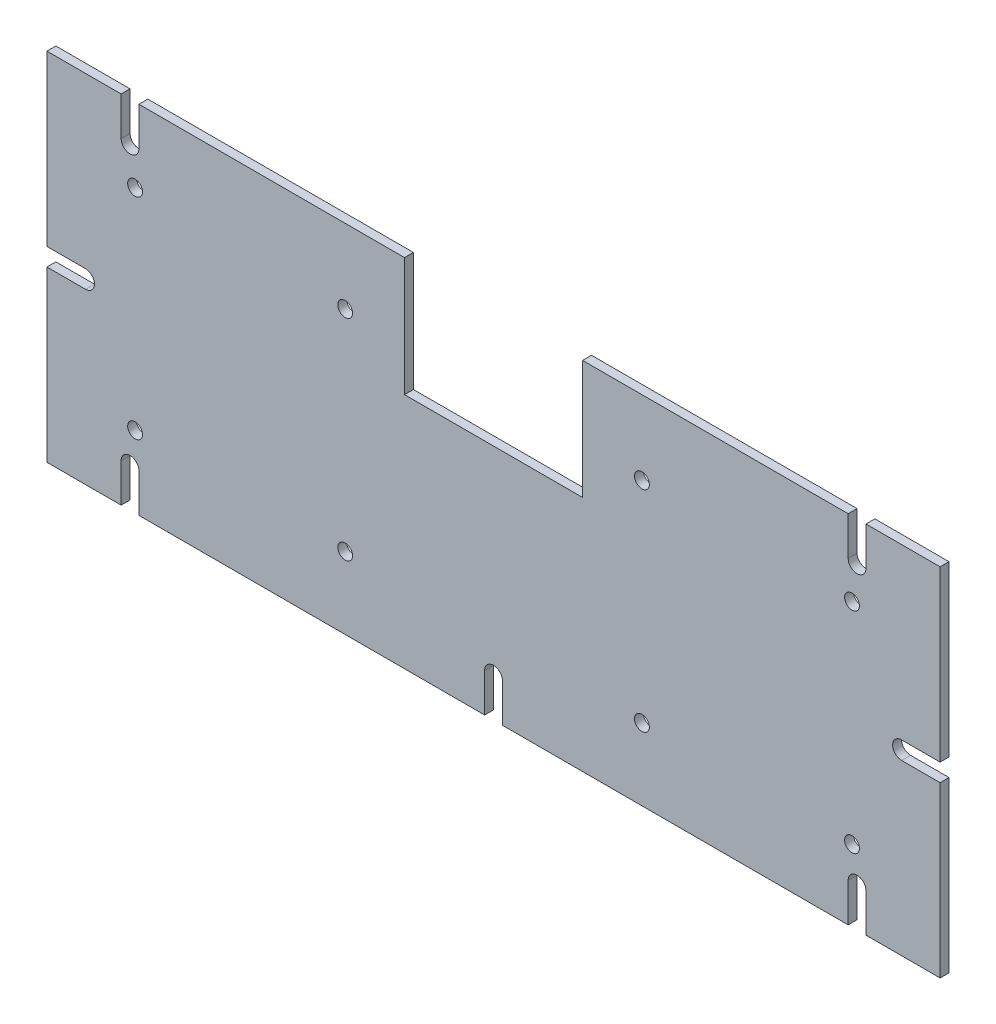
SolidWorks part; units mm, degrees
ref_plane "Front Plane" through (0, 0, 0) normal (0, 0, 1) x (1, 0, 0)
ref_plane "Top Plane" through (0, 0, 0) normal (0, 1, 0) x (1, 0, 0)
ref_plane "Right Plane" through (0, 0, 0) normal (1, 0, 0) x (0, 0, -1)
sketch "Sketch1" plane through (0, 0, 0) normal (0, 0, 1) x (1, 0, 0)
  line L1 (-150.5, -60) -> (150.5, -60)
  line L2 (-150.5, -60) -> (-150.5, 60)
  line L3 (-150.5, 60) -> (150.5, 60)
  line L4 (150.5, -60) -> (150.5, 60)
  line L5 (-150.5, -60) -> (150.5, 60) construction
  line L6 (-150.5, 60) -> (150.5, -60) construction
  point P0 (0, 0)
  dimension "D1" = 301
  dimension "D2" = 120
extrude "Boss-Extrude1" add sketch "Sketch1" along normal blind 3
sketch "Sketch2" plane through (0, 0, 3) normal (0, 0, 1) x (1, 0, 0)
  line L0 (-30, 60) -> (-30, 20)
  line L1 (150.5, 60) -> (-150.5, 60) construction
  line L2 (-30, 20) -> (30, 20)
  line L3 (0, 0) -> (0, 23.4463) construction
  line L4 (30, 60) -> (30, 20)
  line L5 (-30, 60) -> (30, 60)
  line L6 (-150.5, -60) -> (150.5, -60) construction
  point P9 (0, 20)
  point P12 (0, -60)
  dimension "D1" = 30
  dimension "D2" = 40
extrude "Cut-Extrude1" cut sketch "Sketch2" against normal blind 3 contours L5 L4 L2 L0
sketch "Sketch4" plane through (0, 0, 3) normal (0, 0, 1) x (1, 0, 0)
  line L0 (0, 0) -> (0, 20) construction
  line L1 (-30, 20) -> (30, 20) construction
  line L2 (0, 20) -> (0, -60) construction
  line L3 (-150.5, -60) -> (150.5, -60) construction
  line L4 (0, -60) -> (0, 60) construction
  line L5 (-150.5, 0) -> (150.5, 0) construction
  line L6 (150.5, -60) -> (150.5, 60) construction
  line L7 (-125.5, -60) -> (-125.5, -47)
  line L8 (-119.5, -47) -> (-119.5, -60)
  line L9 (-119.5, -60) -> (-125.5, -60)
  line L10 (-150.5, 60) -> (-150.5, -60) construction
  line L11 (3, -47) -> (3, -60)
  line L12 (-3, -60) -> (-3, -47)
  line L13 (3, -60) -> (-3, -60)
  line L14 (125.5, -47) -> (125.5, -60)
  line L15 (119.5, -60) -> (119.5, -47)
  line L16 (125.5, -60) -> (119.5, -60)
  line L17 (0, -20) -> (0, 60) construction
  line L18 (125.5, 60) -> (119.5, 60)
  line L19 (119.5, 60) -> (119.5, 47)
  line L20 (125.5, 47) -> (125.5, 60)
  line L21 (3, 60) -> (-3, 60)
  line L22 (-3, 60) -> (-3, 47)
  line L23 (3, 47) -> (3, 60)
  line L24 (-119.5, 60) -> (-125.5, 60)
  line L25 (-119.5, 47) -> (-119.5, 60)
  line L26 (-125.5, 60) -> (-125.5, 47)
  line L27 (150.5, 3) -> (137.5, 3)
  line L28 (137.5, -3) -> (150.5, -3)
  line L29 (150.5, -3) -> (150.5, 3)
  line L30 (150.5, 3) -> (150.5, -3)
  line L31 (137.5, 3) -> (150.5, 3)
  line L32 (150.5, -3) -> (137.5, -3)
  line L33 (-150.5, -3) -> (-137.5, -3)
  line L34 (-137.5, 3) -> (-150.5, 3)
  line L35 (-150.5, 3) -> (-150.5, -3)
  line L36 (-150.5, -3) -> (-150.5, 3)
  line L37 (-137.5, -3) -> (-150.5, -3)
  line L38 (-150.5, 3) -> (-137.5, 3)
  arc A0 (-125.5, -47) -> (-119.5, -47) centre (-122.5, -47) cw
  arc A1 (-3, -47) -> (3, -47) centre (0, -47) cw
  arc A2 (119.5, -47) -> (125.5, -47) centre (122.5, -47) cw
  arc A3 (119.5, 47) -> (125.5, 47) centre (122.5, 47) ccw
  arc A4 (-3, 47) -> (3, 47) centre (0, 47) ccw
  arc A5 (-125.5, 47) -> (-119.5, 47) centre (-122.5, 47) ccw
  arc A6 (137.5, 3) -> (137.5, -3) centre (137.5, 0) ccw
  arc A7 (-137.5, 3) -> (-137.5, -3) centre (-137.5, 0) cw
  line M21 (-150.5, 60) -> (-150.5, -60)
  line M22 (-150.5, -60) -> (150.5, -60)
  line M23 (150.5, -60) -> (150.5, 60)
  line M24 (150.5, 60) -> (30, 60)
  dimension "D1" = 3
  dimension "D2" = 13
  dimension "D3" = 25
  dimension "D5" = 6
  dimension "D6" = 13
  dimension "D4" = 3
extrude "Cut-Extrude2" cut sketch "Sketch4" against normal blind 10 contours A0 L7 L8 M22 | A7 L34 L33 M21 | A2 L15 L14 M22 | L27 A6 L28 M23 | L19 A3 L20 M24 | L25 L24 L26 A5 | L11 L13 L12 A1 region at (122.5, 52.3073, 3) region at (142.8073, 0, 3) region at (122.5, -52.3073, 3) region at (-122.5, -52.3073, 3) region at (-142.8073, 0, 3)
sketch "Sketch5" plane through (0, 0, 3) normal (0, 0, 1) x (1, 0, 0)
  line L0 (30, 60) -> (30, 20) construction
  line L1 (120.8, -35.8) -> (50, -35.8) construction
  line L2 (120.8, -35.8) -> (120.8, 35) construction
  line L3 (120.8, 35) -> (50, 35) construction
  line L4 (50, -35.8) -> (50, 35) construction
  line L5 (120.8, -35.8) -> (50, 35) construction
  line L6 (120.8, 35) -> (50, -35.8) construction
  line L7 (119.5, 60) -> (30, 60) construction
  circle A0 centre (120.8, 35) radius 2.5
  circle A1 centre (120.8, -35.8) radius 2.5
  circle A2 centre (50, 35) radius 2.5
  circle A3 centre (50, -35.8) radius 2.5
  point P0 (85.4, -0.4)
  dimension "D3" = 5
  dimension "D4" = 5
  dimension "D5" = 5
  dimension "D6" = 5
  dimension "D1" = 70.8
  dimension "D2" = 70.8
  dimension "D7" = 20
  dimension "D8" = 25
extrude "Cut-Extrude3" cut sketch "Sketch5" against normal blind 10 contours A0 | A1 | A3 | A2 region at (120.8, 35, 3) region at (120.8, -35.8, 3) region at (50, -35.8, 3)
ref_plane "Plane1" through (0, 0, 0) normal (-1, 0, 0) x (0, 0, 1)
mirror "Mirror1" about plane through (0, 0, 0) normal (-1, 0, 0) of "Cut-Extrude3"
